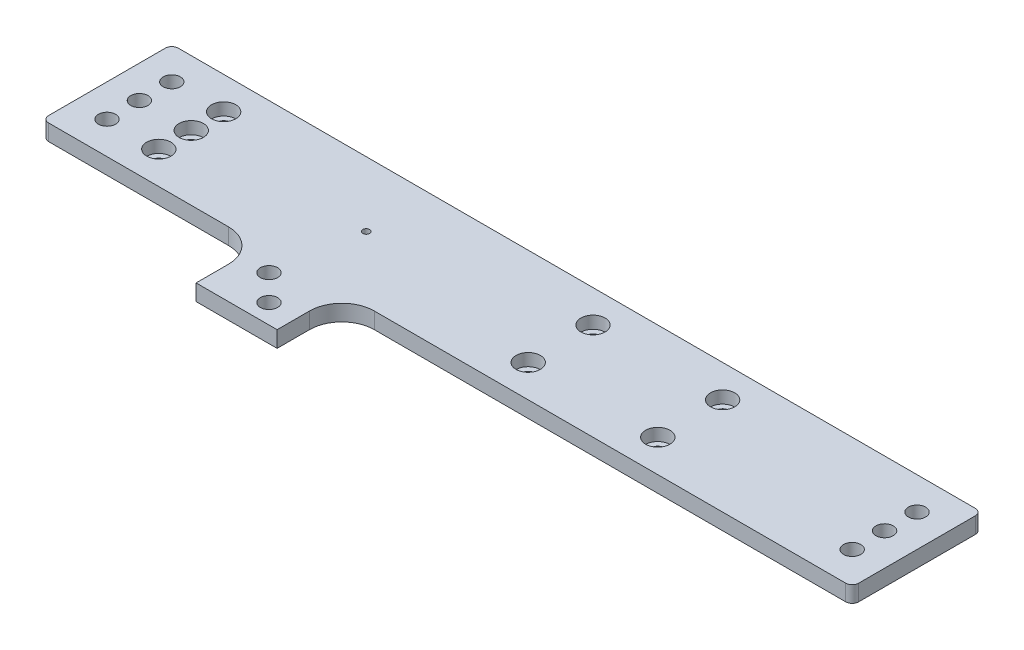
SolidWorks part; units mm, degrees
material "6061-T6 (SS)"
ref_plane "Front" through (0, 0, 0) normal (0, 0, 1) x (1, 0, 0)
ref_plane "Top" through (0, 0, 0) normal (0, 1, 0) x (1, 0, 0)
ref_plane "Right" through (0, 0, 0) normal (1, 0, 0) x (0, 0, -1)
sketch "Sketch1" plane through (0, 0, 0) normal (0, 1, 0) x (1, 0, 0)
  line L1 (-158.75, -25.4) -> (158.75, -25.4)
  line L2 (-158.75, -25.4) -> (-158.75, 25.4)
  line L3 (-158.75, 25.4) -> (158.75, 25.4)
  line L4 (158.75, -25.4) -> (158.75, 25.4)
  line L5 (-158.75, -25.4) -> (158.75, 25.4) construction
  line L6 (-158.75, 25.4) -> (158.75, -25.4) construction
  point P0 (0, 0)
  dimension "D1" = 50.8
  dimension "D2" = 317.5
extrude "Boss-Extrude1" add sketch "Sketch1" along normal blind 6.35
hole_wizard "CBORE for #10 Socket Head Cap Screw1" positions "Sketch2" profile "Sketch4" counterbore size "#10" standard "ANSI Inch" end condition through all
sketch "Sketch2" plane through (0, 6.35, 0) normal (0, 1, 0) x (1, 0, 0)
  line L2 (158.75, 25.4) -> (-158.75, 25.4) construction
  line L6 (-158.75, -25.4) -> (158.75, -25.4) construction
  line L8 (-158.75, 25.4) -> (-158.75, -25.4) construction
  line L12 (158.75, -25.4) -> (158.75, 25.4) construction
  line L15 (19.05, 12.7) -> (19.05, 25.4) construction
  line L17 (19.05, -12.7) -> (19.05, -25.4) construction
  line L18 (-125.73, -25.4) -> (-125.73, -12.7) construction
  line L20 (-125.73, 0) -> (-125.73, 12.7) construction
  line L21 (-125.73, 12.7) -> (-125.73, 25.4) construction
  line L22 (-125.73, 0) -> (-125.73, -12.7) construction
  point P64 (19.05, 12.7)
  point P66 (69.85, 12.7)
  point P68 (19.05, -12.7)
  point P70 (69.85, -12.7)
  point P92 (-125.73, 12.7)
  point P94 (-125.73, 0)
  point P102 (-125.73, -12.7)
  dimension "D2" = 50.8
  dimension "D3" = 25.4
  dimension "D4" = 88.9
  dimension "D5" = 33.02
sketch "Sketch4" plane through (-125.73, 6.35, 12.7) normal (1, 0, 0) x (0, 0, 1)
  line L0 (0, 0) -> (0, 6.35)
  line L1 (0, 6.35) -> (2.5527, 6.35)
  line L3 (2.5527, 6.35) -> (2.5527, 4.826)
  line L4 (2.5527, 4.826) -> (4.7625, 4.826)
  line L5 (4.7625, 4.826) -> (4.7625, 0)
  line L7 (4.7625, 0) -> (0, 0)
  line L11 (0, -6.35) -> (0, 107.95) construction
  dimension "Thru Hole Dia." = 5.1054
  dimension "Thru Hole Depth" = 6.35
  dimension "C'Bore Dia." = 9.525
  dimension "C'Bore Depth" = 4.826
sketch "Sketch7" plane through (0, 0, 0) normal (0, -1, 0) x (1, 0, 0)
  line L0 (-146.05, 25.4) -> (-146.05, 12.7) construction
  line L1 (-158.75, 25.4) -> (158.75, 25.4) construction
  line L2 (-146.05, 12.7) -> (-146.05, 0) construction
  line L3 (-146.05, 0) -> (-146.05, -12.7) construction
  line L4 (-146.05, -12.7) -> (-146.05, -25.4) construction
  line L5 (158.75, -25.4) -> (-158.75, -25.4) construction
  line L7 (-158.75, -25.4) -> (-158.75, 25.4) construction
  line L8 (146.05, 25.4) -> (146.05, 12.7) construction
  line L9 (146.05, 12.7) -> (146.05, 0) construction
  line L10 (146.05, 0) -> (146.05, -12.7) construction
  line L11 (146.05, -12.7) -> (146.05, -25.4) construction
  line L13 (158.75, 25.4) -> (158.75, -25.4) construction
  point P0 (-146.05, 12.7)
  point P2 (-146.05, 0)
  point P4 (-146.05, -12.7)
  point P6 (146.05, 12.7)
  point P8 (146.05, 0)
  point P10 (146.05, -12.7)
  dimension "D1" = 12.7
  dimension "D2" = 12.7
hole_wizard "1/4 Clearance Hole2" positions "Sketch7" profile "Sketch6" hole size "1/4" standard "ANSI Inch" end condition through all
sketch "Sketch6" plane through (-146.05, 0, 12.7) normal (1, 0, 0) x (0, 0, -1)
  line L0 (0, 0) -> (0, 6.35)
  line L1 (0, 6.35) -> (3.3782, 6.35)
  line L2 (3.3782, 6.35) -> (3.3782, 0)
  line L5 (3.3782, 0) -> (0, 0)
  line L11 (0, -6.35) -> (0, 107.95) construction
  dimension "Thru Hole Dia." = 6.7564
  dimension "Thru Hole Depth" = 6.35
sketch "Sketch10" plane through (0, 0, 0) normal (0, -1, 0) x (-1, 0, 0)
  line L0 (158.75, 25.4) -> (158.75, -25.4) construction
  point P0 (57.15, 0)
  dimension "D1" = 101.6
hole_wizard "#6-32 Tapped Hole1" positions "Sketch10" profile "Sketch9" tap size "#6-32" standard "ANSI Inch" end condition through all
sketch "Sketch9" plane through (-57.15, 0, 0) normal (1, 0, 0) x (0, 0, -1)
  line L0 (0, 0) -> (0, 6.35)
  line L1 (0, 6.35) -> (1.3525, 6.35)
  line L2 (1.3525, 6.35) -> (1.3525, 0)
  line L5 (1.3525, 0) -> (0, 0)
  line L11 (0, -6.35) -> (0, 107.95) construction
  dimension "Thru Tap Drill Dia." = 2.7051
  dimension "Thru Tap Drill Depth" = 6.35
cosmetic thread "Hole Thread1" parameters "D2"=3.5052
sketch "Sketch11" plane through (0, 0, 0) normal (0, -1, 0) x (1, 0, 0)
  line L0 (158.75, -25.4) -> (-158.75, -25.4) construction
  line L1 (-70.0118, -25.4) -> (-48.1024, -25.4)
  line L2 (-70.0118, -25.4) -> (-70.0118, -45.81)
  line L3 (-70.0118, -45.81) -> (-48.1024, -45.81)
  line L4 (-48.1024, -25.4) -> (-48.1024, -45.81)
extrude "Boss-Extrude2" [suppressed] add sketch "Sketch11" against normal up to surface (6.35 mm away) up to face at (-57.15, 6.35, -1.3526)
sketch "Sketch12" plane through (0, 6.35, 0) normal (0, 1, 0) x (1, 0, 0)
  line L0 (-158.75, -25.4) -> (158.75, -25.4) construction
  line L1 (-73.025, -25.4) -> (-41.275, -25.4)
  line L2 (-73.025, -25.4) -> (-73.025, -50.8)
  line L3 (-73.025, -50.8) -> (-41.275, -50.8)
  line L4 (-41.275, -25.4) -> (-41.275, -50.8)
  line L5 (-158.75, 25.4) -> (-158.75, -25.4) construction
  dimension "D1" = 85.725
  dimension "D2" = 31.75
  dimension "D3" = 25.4
extrude "Boss-Extrude3" add sketch "Sketch12" against normal up to surface (6.35 mm away) up to face at (-57.15, 0, -1.3526)
sketch "Sketch15" plane through (0, 0, 0) normal (0, -1, 0) x (-1, 0, 0)
  point P0 (52.07, -43.18)
  point P3 (62.23, -33.02)
hole_wizard "1/4 Clearance Hole1" positions "Sketch15" profile "Sketch14" hole size "1/4" standard "ANSI Inch" end condition through all
sketch "Sketch14" plane through (-52.07, 0, 43.18) normal (1, 0, 0) x (0, 0, -1)
  line L0 (0, 0) -> (0, 6.35)
  line L1 (0, 6.35) -> (3.3782, 6.35)
  line L2 (3.3782, 6.35) -> (3.3782, 0)
  line L5 (3.3782, 0) -> (0, 0)
  line L11 (0, -6.35) -> (0, 107.95) construction
  dimension "Thru Hole Dia." = 6.7564
  dimension "Thru Hole Depth" = 6.35
fillet "Fillet1" radius 12.7 2 edges at (-73.025, 3.175, 25.4) (-41.275, 3.175, 25.4)
fillet "Fillet2" radius 2.54 4 edges at (158.75, 3.175, 25.4) (158.75, 3.175, -25.4) (-158.75, 3.175, -25.4) (-158.75, 3.175, 25.4)
